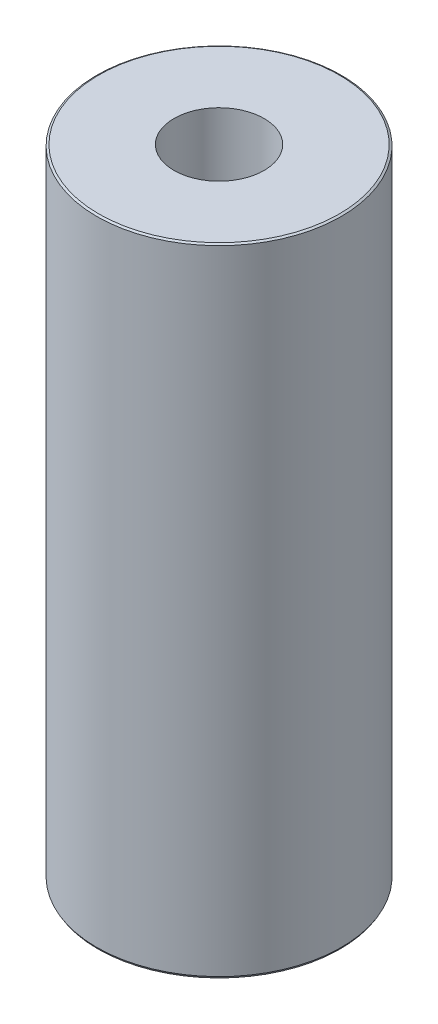
SolidWorks part; units mm, degrees
ref_plane "Front Plane" through (0, 0, 0) normal (0, 0, 1) x (1, 0, 0)
ref_plane "Top Plane" through (0, 0, 0) normal (0, 1, 0) x (1, 0, 0)
ref_plane "Right Plane" through (0, 0, 0) normal (1, 0, 0) x (0, 0, -1)
sketch "Sketch1" plane through (0, 0, 0) normal (0, 1, 0) x (1, 0, 0)
  circle A0 centre (0, 0) radius 22.5
  dimension "SHAFT_OD" = 45
extrude "Boss-Extrude1" add sketch "Sketch1" along normal blind 117.0234
sketch "Sketch2" plane through (0, 0, 0) normal (0, 1, 0) x (1, 0, 0)
  circle A0 centre (0, 0) radius 8.2879
  dimension "BORE_D" = 16.5758
extrude "Cut-Extrude1" cut sketch "Sketch2" along normal through all
chamfer "Chamfer1" distance 0.2139 angle 60 2 edges at (0, 117.0234, 22.5) (0, 0, 22.5) first distance on face at (0, 117.0234, 22.5) first distance on face at (0, 0, 8.2879)
